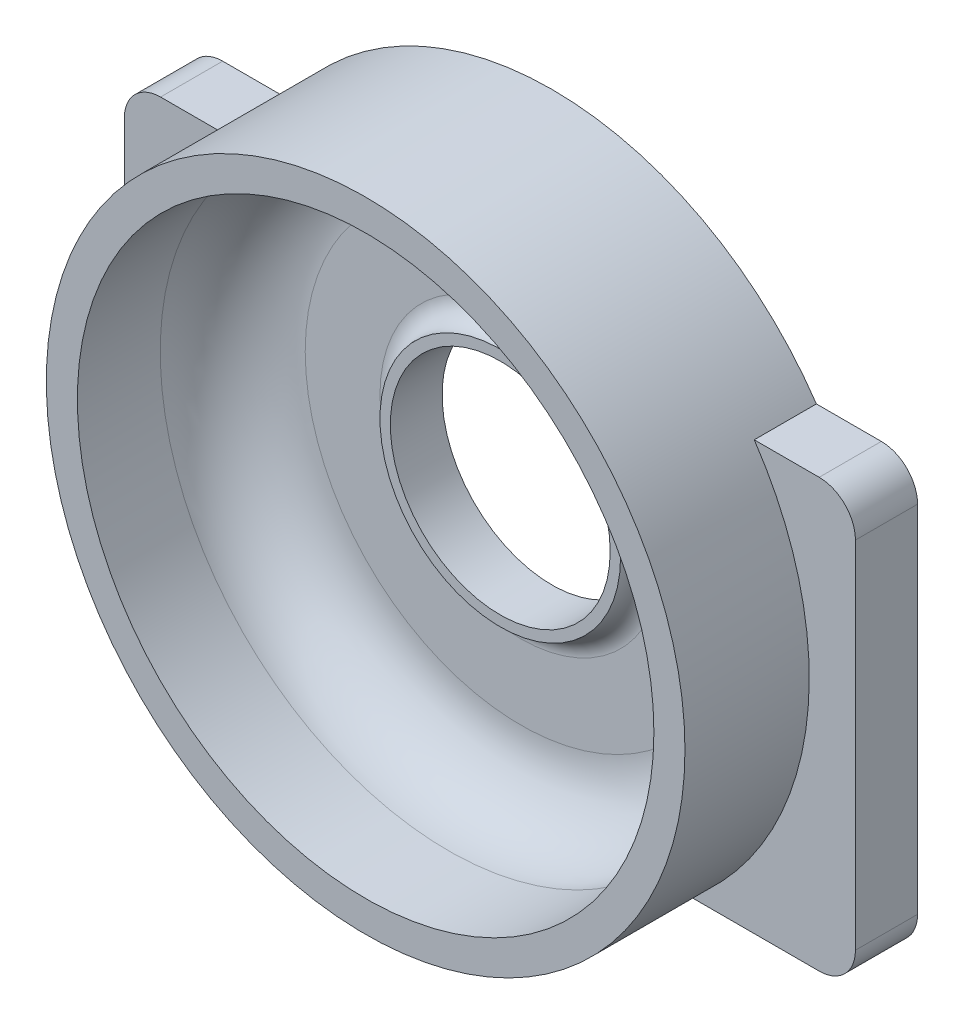
SolidWorks part; units mm, degrees
ref_plane "Front Plane" through (0, 0, 0) normal (0, 0, 1) x (1, 0, 0)
ref_plane "Top Plane" through (0, 0, 0) normal (0, 1, 0) x (1, 0, 0)
ref_plane "Right Plane" through (0, 0, 0) normal (1, 0, 0) x (0, 0, -1)
sketch "Sketch2" plane through (0, 0, 0) normal (0, 0, 1) x (1, 0, 0)
  line L0 (-63.558, 3.3692) -> (-63.558, -6.6308) construction
  line L1 (-63.558, -0.1308) -> (7.042, -0.1308)
  line L2 (-63.558, -0.1308) -> (-63.558, 41.1692)
  line L3 (-63.558, 41.1692) -> (7.042, 41.1692)
  line L4 (7.042, -0.1308) -> (7.042, 41.1692)
  line L5 (7.042, 47.6692) -> (7.042, 37.6692) construction
  line L6 (-53.558, -0.1308) -> (-60.058, -0.1308) construction
  line L7 (-60.058, 41.1692) -> (-53.558, 41.1692) construction
  circle A0 centre (-28.2554, 23.8718) radius 10.6168
  circle A1 centre (-28.2554, 23.8718) radius 30.836
  arc A4 (-63.558, 3.3692) -> (-60.058, -0.1308) centre (-60.058, 3.3692) ccw
  arc A5 (-63.558, 3.3692) -> (-60.058, -0.1308) centre (-60.058, 3.3692) ccw
  arc A13 (-60.058, 41.1692) -> (-63.558, 37.6692) centre (-60.058, 37.6692) ccw
  arc A14 (-60.058, 41.1692) -> (-63.558, 37.6692) centre (-60.058, 37.6692) ccw
  arc A16 (7.042, 37.6692) -> (3.542, 41.1692) centre (3.542, 37.6692) ccw
  arc A17 (7.042, 37.6692) -> (3.542, 41.1692) centre (3.542, 37.6692) ccw
  arc A19 (3.542, -0.1308) -> (7.042, 3.3692) centre (3.542, 3.3692) ccw
  arc A20 (3.542, -0.1308) -> (7.042, 3.3692) centre (3.542, 3.3692) ccw
  circle M7 centre (-58.558, 4.8692) radius 2.3812
  line M8 (-63.558, 9.8692) -> (-63.558, 3.3692)
  arc M9 (-63.558, 3.3692) -> (-60.058, -0.1308) centre (-60.058, 3.3692) ccw
  line M10 (-60.058, -0.1308) -> (-53.558, -0.1308)
  line M11 (-53.558, -0.1308) -> (-53.558, 9.8692)
  line M12 (-53.558, 9.8692) -> (-63.558, 9.8692)
  dimension "D1" = 0
  dimension "D2" = 0
  dimension "D3" = 0
  dimension "D4" = 0
  dimension "D5" = 0
  dimension "D6" = 0
extrude "Boss-Extrude1" add sketch "Sketch2" along normal blind 3 contours A1 L3 L2 M12 | L3 A1 | L3 A1 L1 A0 M12 M11 | L1 A1 | A1 L1 M11 | A1 L1 L4 L3 | A1 M12 M11 | A1 M12 M8 M9 M10 M11 M7 | M7 region at (-62.4329, 0.9943, 0) region at (-51.671, 1.8923, 0) region at (-60.4161, 26.1238, 0) region at (-50.2693, 3.353, 0) region at (-28.2554, -2.8919, 0) region at (-54.3006, 8.6313, 0) region at (2.819, 17.9068, 0) region at (-28.2554, 46.7015, 0) region at (-58.558, 4.8692, 0)
sketch "Sketch3" plane through (0, 0, 3) normal (0, 0, 1) x (1, 0, 0)
  circle A0 centre (-28.2554, 23.8718) radius 30.836
  circle A1 centre (-28.2554, 23.8718) radius 27.836
  arc A2 (-47.6133, -0.1308) -> (-8.8974, -0.1308) centre (-28.2554, 23.8718) ccw construction
  dimension "D1" = 3
  dimension "D2" = 0
extrude "Boss-Extrude2" add sketch "Sketch3" along normal blind 15
fillet "Fillet1" radius 7 1 edges at (-0.4194, 23.8718, 3)
sketch "Sketch4" plane through (0, 0, 3) normal (0, 0, 1) x (1, 0, 0)
  circle A0 centre (-28.2554, 23.8718) radius 10.6168
  circle A1 centre (-28.2554, 23.8718) radius 11.6168
  dimension "D1" = 1
extrude "Boss-Extrude3" add sketch "Sketch4" along normal blind 2
fillet "Fillet2" radius 2 1 edges at (-16.6385, 23.8718, 3)
sketch "Sketch7" plane through (0, 0, 3) normal (0, 0, 1) x (1, 0, 0)
  line L6 (-8.8974, -0.1308) -> (3.542, -0.1308)
  line L7 (7.042, 3.3692) -> (7.042, 37.6692)
  line L8 (3.542, 41.1692) -> (-2.7277, 41.1692)
  line L9 (-8.8974, -0.1308) -> (3.542, -0.1308)
  line L10 (7.042, 3.3692) -> (7.042, 37.6692)
  line L11 (3.542, 41.1692) -> (-2.7277, 41.1692)
  line L15 (-53.783, 41.1692) -> (-60.058, 41.1692)
  line L16 (-63.558, 37.6692) -> (-63.558, 3.3692)
  line L17 (-60.058, -0.1308) -> (-47.6133, -0.1308)
  line L18 (-53.783, 41.1692) -> (-60.058, 41.1692)
  line L19 (-63.558, 37.6692) -> (-63.558, 3.3692)
  line L20 (-60.058, -0.1308) -> (-47.6133, -0.1308)
  arc A6 (-8.8974, -0.1308) -> (-2.7277, 41.1692) centre (-28.2554, 23.8718) ccw
  arc A7 (3.542, -0.1308) -> (7.042, 3.3692) centre (3.542, 3.3692) ccw
  arc A8 (7.042, 37.6692) -> (3.542, 41.1692) centre (3.542, 37.6692) ccw
  arc A9 (-8.8974, -0.1308) -> (-2.7277, 41.1692) centre (-28.2554, 23.8718) ccw
  arc A10 (3.542, -0.1308) -> (7.042, 3.3692) centre (3.542, 3.3692) ccw
  arc A11 (7.042, 37.6692) -> (3.542, 41.1692) centre (3.542, 37.6692) ccw
  arc A15 (-53.783, 41.1692) -> (-47.6133, -0.1308) centre (-28.2554, 23.8718) ccw
  arc A16 (-60.058, 41.1692) -> (-63.558, 37.6692) centre (-60.058, 37.6692) ccw
  arc A17 (-63.558, 3.3692) -> (-60.058, -0.1308) centre (-60.058, 3.3692) ccw
  arc A18 (-53.783, 41.1692) -> (-47.6133, -0.1308) centre (-28.2554, 23.8718) ccw
  arc A19 (-60.058, 41.1692) -> (-63.558, 37.6692) centre (-60.058, 37.6692) ccw
  arc A20 (-63.558, 3.3692) -> (-60.058, -0.1308) centre (-60.058, 3.3692) ccw
  dimension "D1" = 0
  dimension "D2" = 0
extrude "Boss-Extrude4" add sketch "Sketch7" along normal blind 3
sketch "Sketch6" plane through (0, 0, 0) normal (0, 0, -1) x (-1, 0, 0)
  circle A0 centre (58.558, 4.8692) radius 2.3812
  circle A1 centre (58.558, 33.8692) radius 2.3812
  circle A2 centre (-2.042, 33.8692) radius 2.3812
  circle A3 centre (-2.042, 4.8692) radius 2.3813
extrude "Cut-Extrude1" cut sketch "Sketch6" against normal blind 3.175
